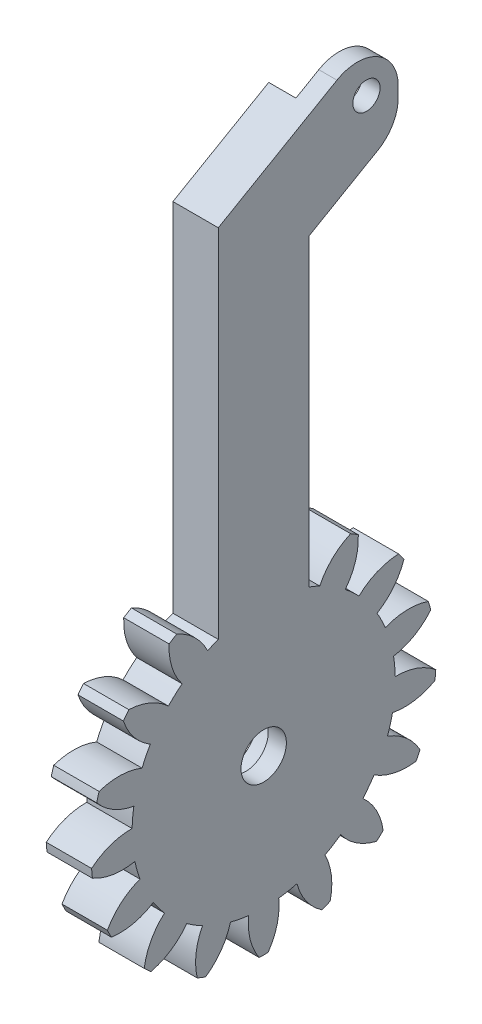
SolidWorks part; units mm, degrees
ref_plane "Plane1" through (0, 0, 0) normal (0, 0, 1) x (1, 0, 0)
ref_plane "Plane2" through (0, 0, 0) normal (0, 1, 0) x (1, 0, 0)
ref_plane "Plane3" through (0, 0, 0) normal (1, 0, 0) x (0, 0, -1)
sketch "HoldingSke" plane through (0, 0, 0) normal (0, 1, 0) x (1, 0, 0)
  line L0 (0, 0) -> (0.4782, -0.1462)
  line L1 (-15, 0) -> (100, 0) construction
  line L2 (0, 0) -> (-2.1039, 2.3779)
  line L3 (0, 0) -> (-11.863, 4.5341)
  line L4 (0, 0) -> (8.2586, 2.5249)
  line L5 (0, 0) -> (-46.8476, -17.4728)
  line L6 (0, 0) -> (-8.2896, -5.593)
  line L7 (-2.1039, 2.3779) -> (8.659, 51.2076)
  line L8 (-76.2, 54.61) -> (-75.3, 54.61)
  line L9 (-71.009, 38.7566) -> (-53.1078, 45.2721)
  line L10 (-76.2, 71.12) -> (104.1128, 71.12)
  line L11 (0, 0) -> (-10, 0)
  line L12 (-76.2, 101.6) -> (-76.133, 101.6)
  line L13 (24.9733, 27.94) -> (52.9518, 28.4284)
  line L14 (24.9733, 27.94) -> (24.9743, 27.94)
  line L15 (24.9733, 27.94) -> (100.4006, 29.5858)
  line L16 (-63.627, -2) -> (-12.827, -2)
  circle A0 centre (0, 0) radius 2.5
  circle A1 centre (0, 0) radius 14.499
  circle A2 centre (0, 0) radius 37.5
  circle A3 centre (0, 0) radius 2.5
  dimension "Num_teeth" = 17
  dimension "Pitch_radius" = 180.3128
  dimension "Width" = 10
  dimension "Thickness" = 10
sketch "BasProSke" plane through (0, 0, 0) normal (0, 1, 0) x (1, 0, 0)
  line L0 (-10, 0) -> (60, 0) construction
  line L1 (0, 0) -> (0, 19)
  line L2 (0, 0) -> (10, 0)
  line L3 (10, 0) -> (10, 19)
  line L4 (10, 19) -> (0, 19)
  dimension "Thickness" = 10
  dimension "Diameter" = 38
revolve "Base-Revolve" add sketch "BasProSke" angle 360 about L0
sketch "TooCutSke" plane through (0, 0, 0) normal (1, 0, 0) x (0, 0, -1)
  line L1 (0, 0) -> (0, 107) construction
  line L2 (0, 0) -> (-1.6857, 16.9162) construction
  line L3 (0, 0) -> (-6.2247, 33.2991) construction
  line L4 (-1.6857, 16.9162) -> (-3.1123, 16.6495) construction
  arc A0 (1.0204, 14.4631) -> (-1.0204, 14.4631) centre (0, 0) ccw
  arc A1 (3.0261, 18.7832) -> (-3.0261, 18.7832) centre (0, 0) ccw
  circle A2 centre (0, 0) radius 17 construction
  circle A3 centre (0, 0) radius 15.9748 construction
  arc A4 (-1.0204, 14.4631) -> (-3.0261, 18.7832) centre (-7.8003, 13.9409) ccw
  arc A5 (3.0261, 18.7832) -> (1.0204, 14.4631) centre (7.8003, 13.9409) ccw
extrude "ToothCut" cut sketch "TooCutSke" along normal through all
fillet "Breaks" [suppressed] radius 0.04 tangent propagation no
fillet "RootFillets" [suppressed] radius 0.501
pattern_circular "TeethCuts" count 17 every 21.176 about axis through (-10, 0, 0) along (1, 0, 0) of "ToothCut", "RootFillets", "Breaks"
sketch "HubNeaOneSke" plane through (0, 0, 0) normal (-1, 0, 0) x (0, 0, 1)
  circle A0 centre (0, 0) radius 14.499
  dimension "Diameter" = 28.998
extrude "HubNearOne" [suppressed] add sketch "HubNeaOneSke" along normal blind 40.0018
sketch "HubNeaBotSke" plane through (0, 0, 0) normal (-1, 0, 0) x (0, 0, 1)
  circle A0 centre (0, 0) radius 14.499
  dimension "Diameter" = 28.998
extrude "HubNearBoth" [suppressed] add sketch "HubNeaBotSke" along normal blind 20.0009
ref_plane "FarPln" through (10, 0, 0) normal (1, 0, 0) x (0, 0, -1)
sketch "HubFarSke" plane through (10, 0, 0) normal (1, 0, 0) x (0, 0, -1)
  circle A0 centre (0, 0) radius 14.499
  dimension "Diameter" = 28.998
extrude "HubFar" [suppressed] add sketch "HubFarSke" along normal blind 20.0009
sketch "BorSke" plane through (0, 0, 0) normal (1, 0, 0) x (0, 0, -1)
  circle A0 centre (0, 0) radius 2.5
  dimension "Diameter" = 5
extrude "Bore" cut sketch "BorSke" along normal mid plane 100.0037
sketch "KeySke" plane through (0, 0, 0) normal (1, 0, 0) x (0, 0, -1)
  line L0 (-1, 0) -> (-1, 3.4)
  line L1 (-1, 3.4) -> (1, 3.4)
  line L2 (1, 3.4) -> (1, 0)
  line L3 (0, 0) -> (0, 34) construction
  line L4 (-1, 0) -> (1, 0)
  dimension "Width" = 2
extrude "Keyway" [suppressed] cut sketch "KeySke" along normal mid plane 100.0037
pattern_circular "Keyway2" [suppressed] count 2 every 90 about axis through (-10, 0, 0) along (1, 0, 0)
sketch "Sketch1" plane through (0, 0, 0) normal (0, 0, 1) x (1, 0, 0)
  line L1 (-5, 20) -> (5, 20)
  line L2 (-5, 20) -> (-5, -20)
  line L3 (-5, -20) -> (5, -20)
  line L4 (5, 20) -> (5, -20)
  line L5 (-5, 20) -> (5, -20) construction
  line L6 (-5, -20) -> (5, 20) construction
  point P0 (0, 0)
  dimension "D1" = 10
  dimension "D2" = 40
extrude "Cut-Extrude1" cut sketch "Sketch1" against normal blind 20 and the other way blind 20
sketch "Sketch2" plane through (5, 0, 0) normal (-1, 0, 0) x (0, 0, 1)
  line L0 (0, 0) -> (0, -21.0725) construction
  line L1 (-3.961, -0.5571) -> (-2, -14.5)
  line L2 (4, 0) -> (2, -14.5)
  circle A0 centre (0, 0) radius 4
  circle A1 centre (0, -14.5) radius 2
  dimension "D1" = 8
  dimension "D2" = 4
  dimension "D3" = 14.5
sketch "Sketch4" plane through (10, 0, 0) normal (1, 0, 0) x (0, 0, -1)
  line L0 (0, 0) -> (0, 50) construction
  line L1 (0, 50) -> (17.3205, 60) construction
  line L2 (5, 0) -> (5, 47.1132)
  line L3 (5, 47.1132) -> (14.8205, 52.7831)
  line L4 (-5, 0) -> (-5, 52.8868)
  line L5 (-5, 52.8868) -> (14.8205, 64.3301)
  line L6 (14.8205, 64.3301) -> (14.8205, 52.7831)
  line L7 (-5, 0) -> (-2.5, 0)
  line L8 (5, 47.1132) -> (19.8205, 55.6699) construction
  line L9 (2.5, 0) -> (5, 0)
  circle A0 centre (0, 0) radius 2.5 construction
  arc A1 (2.5, 0) -> (-2.5, 0) centre (0, 0) ccw
  dimension "D1" = 120
  dimension "D2" = 50
  dimension "D3" = 20
  dimension "D4" = 5
  dimension "D5" = 5
extrude "Boss-Extrude1" add sketch "Sketch4" against normal blind 5
sketch "Sketch5" plane through (5, 0, 0) normal (-1, 0, 0) x (0, 0, 1)
  circle A0 centre (0, 0) radius 2.5 construction
  circle A1 centre (0, 0) radius 2.5
  circle A2 centre (0, 0) radius 4.75
  dimension "D1" = 9.5
extrude "Cut-Extrude2" cut sketch "Sketch5" against normal blind 3
sketch "Sketch6" plane through (5, 0, 0) normal (-1, 0, 0) x (0, 0, 1)
  line L1 (-14.8205, 52.7831) -> (-14.8205, 64.3301) construction
  circle A0 centre (-11.3205, 57.3301) radius 1.5
  point P2 (0, 0)
  dimension "D1" = 3
  dimension "D2" = 7
  dimension "D3" = 3.5
extrude "Cut-Extrude3" cut sketch "Sketch6" against normal through all
sketch "Sketch7" plane through (5, 0, 0) normal (-1, 0, 0) x (0, 0, 1)
  line L0 (-11.3205, 57.3301) -> (-18.8552, 61.6803) construction
  line L1 (-14.8205, 64.3301) -> (5, 52.8868) construction
  line L2 (-8.3205, 62.5263) -> (-15.8552, 66.8765)
  line L3 (-14.3205, 52.134) -> (-21.8552, 56.4842)
  line L4 (-21.8552, 56.4842) -> (-15.8552, 66.8765)
  circle A0 centre (-11.3205, 57.3301) radius 6
  dimension "D1" = 12
  dimension "D2" = 6
  dimension "D3" = 6
extrude "Cut-Extrude4" cut sketch "Sketch7" against normal blind 3 contours A0 L0 L4 L3 | A0 | L0 A0 L2 L4 region at (5, 57.5087, -18.7016) region at (5, 63.6331, -15.1657) region at (5, 62.9618, -12.8295)
fillet "Fillet1" radius 4.5 2 edges at (9, 52.7831, -14.8205) (9, 64.3301, -14.8205)
fillet "Fillet2" radius 4.5 1 edges at (6.5, 51.4493, -12.5102)
equation "' \"Module@HoldingSke\" = 6.35"
equation "' \"Num_teeth@HoldingSke\" = 12"
equation "' \"Ap@HoldingSke\" =  20"
equation "' \"Ap@HoldingSke\" = 20"
equation "'\"Width@HoldingSke\" = 0.2.5 * 25.4"
equation "' \"Hub_dia@HoldingSke\"= 1 * 25.4"
equation "' \"Hub_dia@HoldingSke\" = 1 * 25.4"
equation "' \"Overall_len@HoldingSke\" = 1.0 * 25.4"
equation "' \"Bore@HoldingSke\" = 0.75 * 25.4"
equation "' \"T_dim@HoldingSke\" = 0.1 * 25.4"
equation "' \"Width@KeySke\" = 0.25 * 25.4"
equation "' \"Show_teeth@HoldingSke\" = 13"
equation "' \"Backlash@HoldingSke\" = 0.009 * 25.4"
equation "' \"Addendum_fac@HoldingSke\" = 1.0"
equation "' \"Dedendum_fac@HoldingSke\" = 1.25"
equation "' \"Dedendum_add@HoldingSke\" = 0.00005 * 25.4"
equation "' \"Clearance_fac@HoldingSke\" = 0.25"
equation "\"Pitch@HoldingSke\" = 1 / \"Module@HoldingSke\""
equation "\"Overcut_dia@TooCutSke\" = (\"Num_teeth@HoldingSke\" + 2 * \"Addendum_fac@HoldingSke\") / \"Pitch@HoldingSke\" + 0.002 * 25.4"
equation "\"Pitch_dia@TooCutSke\" = \"Num_teeth@HoldingSke\" / \"Pitch@HoldingSke\""
equation "\"Base_dia@TooCutSke\" = \"Num_teeth@HoldingSke\" / \"Pitch@HoldingSke\" * cos((\"Ap@HoldingSke\"  * 3.14159265 / 180))"
equation "\"Root_dia@TooCutSke\" = (\"Num_teeth@HoldingSke\" + 2) / \"Pitch@HoldingSke\" - 2 * (\"Addendum_fac@HoldingSke\" + \"Dedendum_fac@HoldingSke\") / \"Pitch@HoldingSke\" - \"Dedendum_add@HoldingSke\" * 2"
equation "\"Half_ang@TooCutSke\" = 180 / \"Num_teeth@HoldingSke\""
equation "\"Half_CT@TooCutSke\" = \"Num_teeth@HoldingSke\" / \"Pitch@HoldingSke\" * sin((3.14159265 / 2 / \"Num_teeth@HoldingSke\")) / 2 - 7 * \"Backlash@HoldingSke\" / 4"
equation "\"Flank_rad@TooCutSke\" = \"Num_teeth@HoldingSke\" / \"Pitch@HoldingSke\" / 5"
equation "\"Radius@RootFillets\" = \"Clearance_fac@HoldingSke\" / \"Pitch@HoldingSke\" + \"Dedendum_add@HoldingSke\""
equation "\"Break_rad@Breaks\" = 0.02 / \"Pitch@HoldingSke\""
equation "\"Thickness@HoldingSke\" = \"Width@HoldingSke\""
equation "\"OAL@HoldingSke\" = \"Thickness@HoldingSke\""
equation "\"MHD@HoldingSke\" = (\"Num_teeth@HoldingSke\" + 2) / \"Pitch@HoldingSke\" - 2 * (\"Addendum_fac@HoldingSke\" + \"Dedendum_fac@HoldingSke\")  / \"Pitch@HoldingSke\" - \"Dedendum_add@HoldingSke\" * 2"
equation "\"MBD@HoldingSke\" = (\"Num_teeth@HoldingSke\" + 2) / \"Pitch@HoldingSke\" - 2 * (\"Addendum_fac@HoldingSke\" + \"Dedendum_fac@HoldingSke\")  / \"Pitch@HoldingSke\" - \"Dedendum_add@HoldingSke\" * 2 - 0.002 * 25.4"
equation "\"MHD@HoldingSke\" = ((sgn( \"MHD@HoldingSke\" - \"Hub_dia@HoldingSke\" )-1)*( \"MHD@HoldingSke\" - \"Hub_dia@HoldingSke\" ))/-2+ \"Hub_dia@HoldingSke\""
equation "\"MBD@HoldingSke\" = ((sgn( \"MBD@HoldingSke\" - \"Bore@HoldingSke\" )-1)*( \"MBD@HoldingSke\" - \"Bore@HoldingSke\" ))/-2+ \"Bore@HoldingSke\""
equation "\"OAL@HoldingSke\" = ((sgn( \"OAL@HoldingSke\" - \"Overall_len@HoldingSke\" )+1)*( \"OAL@HoldingSke\" - \"Overall_len@HoldingSke\" ))/2 + \"Overall_len@HoldingSke\" + 0.000002 * 25.4"
equation "\"Num_teeth@TeethCuts\" = int( \"Show_teeth@HoldingSke\" ) + 1"
equation "\"Num_teeth@TeethCuts\" = ((sgn( \"Num_teeth@TeethCuts\" - \"Num_teeth@HoldingSke\" )-1)*( \"Num_teeth@TeethCuts\" - \"Num_teeth@HoldingSke\" ))/-2+ \"Num_teeth@HoldingSke\""
equation "\"Num_teeth@TeethCuts\" = ((sgn( \"Num_teeth@TeethCuts\" - 2.0)+1)*( \"Num_teeth@TeethCuts\" - 2.0))/2 +2.0"
equation "\"Angle@TeethCuts\" = 360.0 / \"Num_teeth@HoldingSke\""
equation "\"Diameter@BasProSke\" = (\"Num_teeth@HoldingSke\" + 2 * \"Addendum_fac@HoldingSke\") / \"Pitch@HoldingSke\""
equation "\"Thickness@BasProSke\"  = \"Thickness@HoldingSke\""
equation "' \"Fillet_rad@BasProSke\" =  \"Thickness@HoldingSke\" * 0.05"
equation "' \"Fillet_rad@BasProSke\" = \"Thickness@HoldingSke\" * 0.05"
equation "\"MHD@HoldingSke\" = ((sgn( \"MHD@HoldingSke\" - \"Root_dia@TooCutSke\" )-1)*( \"MHD@HoldingSke\" - \"Root_dia@TooCutSke\" ))/-2+ \"Root_dia@TooCutSke\""
equation "\"Diameter@HubNeaOneSke\" = \"MHD@HoldingSke\""
equation "\"Length@HubNearOne\" = \"OAL@HoldingSke\" - \"Thickness@BasProSke\""
equation "\"Diameter@HubNeaBotSke\" = \"MHD@HoldingSke\""
equation "\"Length@HubNearBoth\" = ( \"OAL@HoldingSke\" - \"Thickness@BasProSke\" ) / 2.0"
equation "\"Thickness@FarPln\" = \"Thickness@BasProSke\""
equation "\"Diameter@HubFarSke\" = \"MHD@HoldingSke\""
equation "\"Length@HubFar\" = ( \"OAL@HoldingSke\" - \"Thickness@BasProSke\" ) / 2.0"
equation "\"Diameter@BorSke\" = \"MBD@HoldingSke\""
equation "\"D1@Bore\" = \"OAL@HoldingSke\" * 2.0"
equation "\"D1@Keyway\" = \"OAL@HoldingSke\" * 2.0"
equation "\"Offset@KeySke\" = \"T_dim@HoldingSke\" + \"MBD@HoldingSke\" / 2.0"
